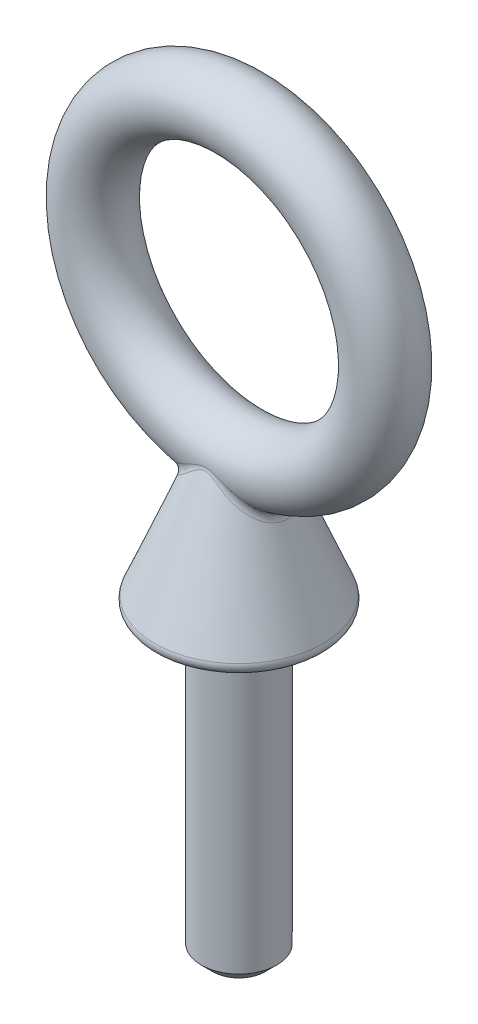
SolidWorks part; units mm, degrees
ref_plane "Front Plane" through (0, 0, 0) normal (0, 0, 1) x (1, 0, 0)
ref_plane "Top Plane" through (0, 0, 0) normal (0, 1, 0) x (1, 0, 0)
ref_plane "Right Plane" through (0, 0, 0) normal (1, 0, 0) x (0, 0, -1)
sketch "Sketch1" plane through (0, 0, 0) normal (0, 0, 1) x (1, 0, 0)
  line L0 (0, -15.0812) -> (0, -49.2125) construction
  line L1 (-3.175, -49.2125) -> (3.175, -49.2125) construction
  line L2 (3.3125, -49.1331) -> (3.3125, -50.4031) construction
  line L3 (0, -15.0812) -> (0, -9.525) construction
  line L4 (-7.1437, -23.8125) -> (7.1438, -23.8125) construction
  line L5 (3.3125, -50.4031) -> (2.2126, -49.7681) construction
  line L6 (2.2126, -49.7681) -> (3.3125, -49.1331) construction
  line L7 (2.2126, -49.7681) -> (2.3501, -49.7681) construction
  line L8 (3.3125, -49.7681) -> (3.175, -49.7681) construction
  line L9 (2.3501, -49.8475) -> (2.3501, -49.6887) construction
  line L10 (3.175, -50.3238) -> (3.175, -49.2125) construction
  line L11 (3.2437, -50.3634) -> (3.2437, -49.1728) construction
  circle A0 centre (0, 0) radius 15.0813 construction
  circle A1 centre (0, 12.3031) radius 2.7781 construction
  circle A2 centre (0, 0) radius 9.525 construction
  point P7 (0, -15.0812)
  point P9 (0, -23.8125)
  point P10 (0, 15.0812)
  point P11 (0, 9.525)
  point P14 (0, -49.2125)
  point P17 (0, 0)
  point P19 (0, -12.3031)
  point P21 (0, -23.8125)
  point P32 (2.3501, -49.7681)
  point P35 (3.175, -49.7681)
  point P38 (3.2437, -49.7681)
  dimension "Pitch" = 1.27
  dimension "D1" = 0.1588
sketch "Sketch2" plane through (0, 0, 0) normal (0, 1, 0) x (1, 0, 0)
  circle A0 centre (0, 0) radius 3.175
extrude "Boss-Extrude1" add sketch "Sketch2" against normal up to vertex (49.2125 mm away) from vertex up to point (0, -49.2125, 0) starting at point (0, -23.8125, 0)
sketch "Sketch3" [suppressed] plane through (0, -49.2125, 0) normal (0, -1, 0) x (1, 0, 0)
  circle A1 centre (0, 0) radius 3.175
  circle A2 centre (0, 0) radius 3.175
  point P0 (3.175, 0)
  point P1 (0, -3.175)
  dimension "D1" = 0
sketch "Sketch4" [suppressed] plane through (0, 0, 0) normal (0, 0, 1) x (1, 0, 0)
  line L0 (2.3501, -49.6887) -> (2.3501, -49.8475)
  line L1 (2.3501, -49.8475) -> (3.2437, -50.3634)
  line L2 (3.2437, -50.3634) -> (3.2437, -49.1728)
  line L3 (3.2437, -49.1728) -> (2.3501, -49.6887)
sketch "Sketch5" plane through (0, -49.2125, 0) normal (0, -1, 0) x (1, 0, 0)
  circle A0 centre (0, 0) radius 2.2126
extrude "Cut-Extrude1" cut sketch "Sketch5" against normal through all draft 45 flip side to cut
sketch "Sketch6" plane through (0, 0, 0) normal (1, 0, 0) x (0, 0, -1)
  circle A0 centre (0, 12.3031) radius 2.7781
ref_axis "Axis1" through (0, 0, -7.6398) along (0, 0, 1)
revolve "Revolve1" add sketch "Sketch6" angle 360 about axis through (0, 0, -7.6398) along (0, 0, 1)
sketch "Sketch8" plane through (0, 0, 0) normal (0, 0, 1) x (1, 0, 0)
  line L0 (0, -23.8125) -> (0, -12.3031)
  line L1 (0, -12.3031) -> (-2.7781, -12.3031)
  line L2 (-6.4492, -23.8125) -> (-7.1437, -23.8125) construction
  line L3 (-7.1437, -23.8125) -> (-7.1437, -23.118) construction
  line L4 (0, -23.8125) -> (7.1437, -23.8125) construction
  line L5 (-7.1437, -23.8125) -> (7.1438, -23.8125) construction
  line L6 (-7.0921, -22.8551) -> (-2.7781, -12.3031)
  line L7 (-7.1437, -23.8125) -> (0, -23.8125) construction
  line L9 (-6.4492, -23.8125) -> (0, -23.8125)
  arc A0 (-7.0921, -22.8551) -> (-6.4492, -23.8125) centre (-6.4492, -23.118) ccw
  circle A1 centre (0, -12.3031) radius 2.7781 construction
  dimension "D1" = 0.6945
revolve "Revolve2" add sketch "Sketch8" angle 360 about L0
fillet "Fillet1" radius 0.6945 1 edges at (3.2544, -14.2744, 1.5013)
sketch "SketchX" plane through (0, 0, 0) normal (1, 0, 0) x (0, 0, -1)
  line L0 (3.175, -49.2125) -> (3.175, -46.0375) construction
  line L1 (0, -49.2125) -> (3.175, -49.2125) construction
  dimension "D1" = 3.175
  dimension "D2" = 3.175
ref_axis "Center Axis 1" through (0, 21.5506, 0) along (0, -1, 0)
ref_axis "Center Axis 2" through (0, 0, -7.6398) along (0, 0, 1)
curve "Helix/Spiral1" [suppressed] pitch 1.27 height 26.67 turns 21 parameters "Pitch"=1.27
ref_plane "Plane1" [suppressed] through (0, -23.8125, 0) normal (0, -1, 0) x (1, 0, 0)
split "Split1" [suppressed] bodies to split 109
sweep "Cut-Sweep1" [suppressed] cut profiles "Sketch4" path "Helix/Spiral1"
sketch "Sketch9" [suppressed] plane through (0, -23.8125, 0) normal (0, -1, 0) x (1, 0, 0)
  line L0 (-7.1437, 0) -> (7.1438, 0) construction
  circle A0 centre (0, 0) radius 3.175
extrude "Boss-Extrude2" [suppressed] add sketch "Sketch9" along normal blind 2.54 draft 45
equation "\"D3@Helix/Spiral1\" = \"Pitch@Helix/Spiral1\" + \"Thread Lg.@Sketch1\""
equation "\"D1@Sketch8\" = \"A@Sketch1\" / 8"
equation "\"D1@Fillet1\" = \"A@Sketch1\" / 8"
equation "\"D1@SketchX\"= \"Pitch@Helix/Spiral1\"*2.5"
equation "\"D1@Sketch1\"=\"Pitch@Sketch1\"/8"
equation "\"Pitch@Helix/Spiral1\"=\"Pitch@Sketch1\""
equation "\"D2@SketchX\" = \"Thread OD@Sketch1\" / 2"
